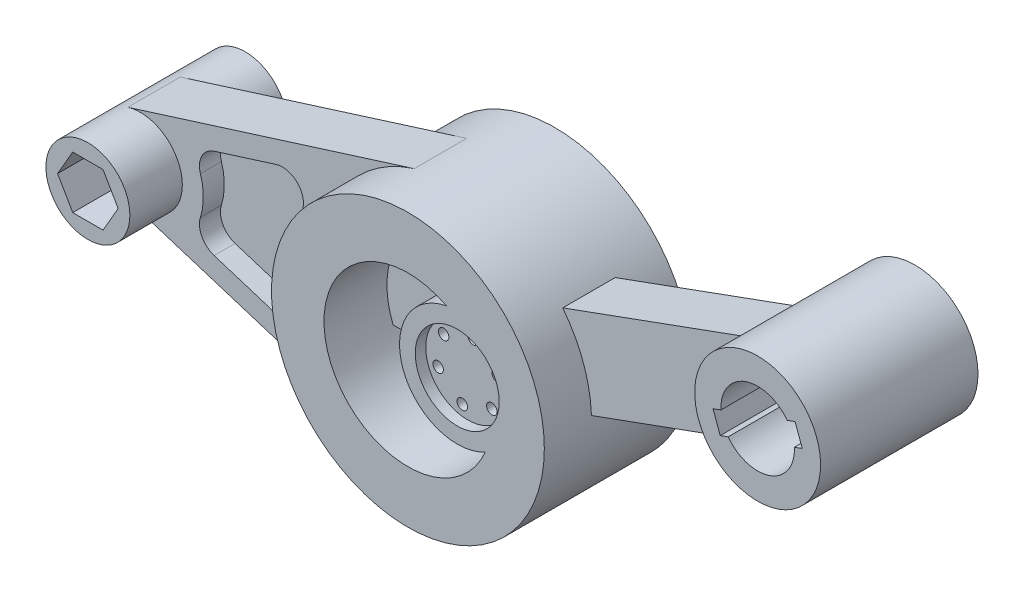
SolidWorks part; units mm, degrees
material "Copper"
ref_plane "Front Plane" through (0, 0, 0) normal (0, 0, 1) x (1, 0, 0)
ref_plane "Top Plane" through (0, 0, 0) normal (0, 1, 0) x (1, 0, 0)
ref_plane "Right Plane" through (0, 0, 0) normal (1, 0, 0) x (0, 0, -1)
ref_plane "CENTRE_Plane" through (150, 0, 0) normal (1, 0, 0) x (0, 0, -1)
ref_axis "CENTRE_Plane_Axis" through (150, 0, 33) along (0, 0, -1)
ref_plane "CENTRE_RIGHT_Plane" through (132.4533, 48.2091, 0) normal (0.9397, 0.342, 0) x (0, 0, -1)
ref_plane "RIGHT_Plane" through (301.598, 109.7727, 0) normal (0.9397, 0.342, 0) x (0, 0, -1)
sketch "Sketch1" plane through (0, 0, 0) normal (0, 0, 1) x (1, 0, 0)
  line L0 (-6, 19.0788) -> (130.5, 62.006)
  line L1 (-6, -19.0788) -> (130.5, -62.006)
  arc A0 (-6, 19.0788) -> (-6, -19.0788) centre (0, 0) ccw
  arc A1 (130.5, -62.006) -> (130.5, 62.006) centre (150, 0) ccw
  dimension "D1" = 40
  dimension "D2" = 130
extrude "LEFT_ARM" add sketch "Sketch1" along normal mid plane 25
sketch "Sketch2" plane through (0, 0, 0) normal (0, 0, 1) x (1, 0, 0)
  circle A0 centre (0, 0) radius 20
  dimension "D1" = 40
extrude "LEFT_Boss" add sketch "Sketch2" along normal mid plane 75
sketch "Sketch4" plane through (0, 0, 37.5) normal (0, 0, 1) x (1, 0, 0)
  line L0 (38.5, 0) -> (-38.5, 0) construction
  line L1 (14.4338, 0) -> (7.2169, 12.5)
  line L2 (7.2169, 12.5) -> (-7.2169, 12.5)
  line L3 (-7.2169, 12.5) -> (-14.4338, 0)
  line L4 (-14.4338, 0) -> (-7.2169, -12.5)
  line L5 (-7.2169, -12.5) -> (7.2169, -12.5)
  line L6 (7.2169, -12.5) -> (14.4338, 0)
  circle A0 centre (0, 0) radius 12.5 construction
  dimension "D1" = 25
extrude "LEFT_Hex" cut sketch "Sketch4" against normal through all both and the other way through all
sketch "Sketch3" plane through (0, 0, 0) normal (0, 0, 1) x (1, 0, 0)
  circle A0 centre (150, 0) radius 65
  dimension "D1" = 130
extrude "CENTRE_Boss" add sketch "Sketch3" along normal mid plane 70
sketch "Sketch5" plane through (132.4533, 48.2091, 0) normal (0.9397, 0.342, 0) x (0, 0, -1)
  line L0 (-33, -51.303) -> (33, -51.303) construction
  line L1 (-12.5, -71.303) -> (12.5, -71.303)
  line L2 (-12.5, -71.303) -> (-12.5, -31.303)
  line L3 (-12.5, -31.303) -> (12.5, -31.303)
  line L4 (12.5, -71.303) -> (12.5, -31.303)
  line L5 (-12.5, -71.303) -> (12.5, -31.303) construction
  line L6 (-12.5, -31.303) -> (12.5, -71.303) construction
  line L7 (0, 86.11) -> (0, -86.11) construction
  point P0 (0, -51.303)
  dimension "D1" = 25
  dimension "D2" = 40
extrude "RIGHT_ARM" add sketch "Sketch5" along normal up to surface (180 mm away) up to plane "RIGHT_Plane"
sketch "RIGHT_ARM_CL" plane through (0, 0, 0) normal (0, 0, 1) x (1, 0, 0)
  line L0 (150, 0) -> (319.1447, 61.5636) construction
  line L1 (321.8248, 54.2) -> (281.3712, 165.3454) construction
sketch "Sketch7" plane through (0, 0, 0) normal (0, 0, 1) x (1, 0, 0)
  circle A0 centre (319.1447, 61.5636) radius 30
  dimension "D1" = 60
extrude "RIGHT_Boss" add sketch "Sketch7" along normal mid plane 75
sketch "Sketch8" plane through (0, 0, 37.5) normal (0, 0, 1) x (1, 0, 0)
  circle A0 centre (319.1447, 61.5636) radius 17.5
  dimension "D1" = 35
extrude "RIGHT_Boss_Hole" cut sketch "Sketch8" against normal through all
sketch "Sketch9" plane through (0, 0, 35) normal (0, 0, 1) x (1, 0, 0)
  circle A0 centre (150, 0) radius 40
  dimension "D1" = 80
extrude "CENTRE_Hole" cut sketch "Sketch9" against normal through all
sketch "Sketch10" plane through (0, 0, 0) normal (0, 0, 1) x (1, 0, 0)
  line L0 (150, 0) -> (319.1447, 61.5636) construction
  line L1 (153.1456, -8.6423) -> (111.7611, 105.0605) construction
  circle A0 centre (173.4923, 8.5505) radius 27.5
  dimension "D1" = 55
  dimension "D2" = 25
extrude "CENTRE_Blob" add sketch "Sketch10" along normal mid plane 70
sketch "Sketch11" plane through (150, 0, 0) normal (1, 0, 0) x (0, 0, -1)
  line L1 (-5, -15) -> (5, -15)
  line L2 (-5, -15) -> (-5, 15)
  line L3 (-5, 15) -> (5, 15)
  line L4 (5, -15) -> (5, 15)
  line L5 (-5, -15) -> (5, 15) construction
  line L6 (-5, 15) -> (5, -15) construction
  point P0 (0, 0)
  dimension "D1" = 10
  dimension "D2" = 30
extrude "CENTRE_Beam" add sketch "Sketch11" along normal up to next and the other way up to next
sketch "Sketch12" plane through (0, 0, 35) normal (0, 0, 1) x (1, 0, 0)
  circle A0 centre (173.4923, 8.5505) radius 20
  dimension "D1" = 40
extrude "Cut-Extrude4" cut sketch "Sketch12" against normal blind 5
hole_wizard "M6x1.0 Tapped Hole1" positions "Sketch13" profile "Sketch14" tap size "M6x1.0" standard "ANSI Metric" end condition up to next
sketch "Sketch13" plane through (0, 0, 30) normal (0, 0, 1) x (1, 0, 0)
  line L0 (150, 0) -> (319.1447, 61.5636) construction
  circle A0 centre (173.4923, 8.5505) radius 20 construction
  point P0 (159.3969, 3.4202)
  dimension "D1" = 15
sketch "Sketch14" plane through (159.3969, 3.4202, 30) normal (1, 0, 0) x (0, -1, 0)
  line L0 (0, 0) -> (0, 65)
  line L1 (0, 65) -> (2.5, 65)
  line L2 (2.5, 65) -> (2.5, 0)
  line L5 (2.5, 0) -> (0, 0)
  line L11 (0, -6.35) -> (0, 107.95) construction
  dimension "Thru Tap Drill Dia." = 5
  dimension "Thru Tap Drill Depth" = 65
cosmetic thread "Hole Thread1" parameters "D2"=6
pattern_circular "CirPattern1" count 6 over 360 about axis through (173.4923, 8.5505, 30) along (0, 0, 1) of "M6x1.0 Tapped Hole1"
cosmetic thread "Hole Thread2" parameters "D2"=6
cosmetic thread "Hole Thread3" parameters "D2"=6
cosmetic thread "Hole Thread4" parameters "D2"=6
cosmetic thread "Hole Thread5" parameters "D2"=6
cosmetic thread "Hole Thread6" parameters "D2"=6
cosmetic thread "Hole Thread7" parameters "D2"=6
cosmetic thread "Hole Thread8" parameters "D2"=6
mirror "Mirror1" about plane through (0, 0, 0) normal (0, 0, 1) of "Cut-Extrude4"
sketch "Sketch15" plane through (0, 0, 12.5) normal (0, 0, 1) x (1, 0, 0)
  line L24 (84.8585, 37.1696) -> (-3, 9.5394)
  line L25 (-3, -9.5394) -> (84.8585, -37.1696)
  line L26 (84.8585, 37.1696) -> (23.9815, 18.0247)
  line L27 (23.9815, -18.0247) -> (84.8585, -37.1696)
  arc A12 (84.8585, 37.1696) -> (84.8585, -37.1696) centre (150, 0) ccw
  arc A13 (84.8585, 37.1696) -> (84.8585, -37.1696) centre (150, 0) ccw
  arc A23 (-9, -28.6182) -> (-9, 28.6182) centre (0, 0) ccw
  arc A24 (23.9815, -18.0247) -> (23.9815, 18.0247) centre (0, 0) ccw
  dimension "D1" = 10
  dimension "D2" = 10
extrude "Cut_OUT" cut sketch "Sketch15" against normal blind 10
fillet "Fillet1" radius 10 4 edges at (84.8585, 37.1696, 7.5) (84.8585, -37.1696, 7.5) (23.9815, -18.0247, 7.5) (23.9815, 18.0247, 7.5)
mirror "Mirror2" about plane through (0, 0, 0) normal (0, 0, 1) of "Fillet1", "Cut_OUT"
sketch "Sketch16" plane through (0, 0, 0) normal (0, 0, 1) x (1, 0, 0)
  line L0 (320.8548, 56.8652) -> (317.4346, 66.2621)
  line L1 (321.8248, 54.2) -> (281.3712, 165.3454) construction
  line L2 (317.4346, 66.2621) -> (297.889, 59.1481)
  line L3 (297.889, 59.1481) -> (301.3092, 49.7511)
  line L4 (301.3092, 49.7511) -> (320.8548, 56.8652)
  circle A0 centre (319.1447, 61.5636) radius 17.5 construction
  point P4 (319.1447, 61.5636)
  dimension "D1" = 10
  dimension "D2" = 20.8
extrude "KEYWAY" cut sketch "Sketch16" against normal through all both and the other way through all
mirror "Mirror3" about plane through (301.598, 109.7727, 0) normal (0.9397, 0.342, 0) of "KEYWAY"
equation "\"D1@Sketch2\"=\"D1@Sketch1\""
equation "\"D1@Sketch3\"=\"D2@Sketch1\""
equation "\"D2@Sketch16\"=17.5+3.3"
